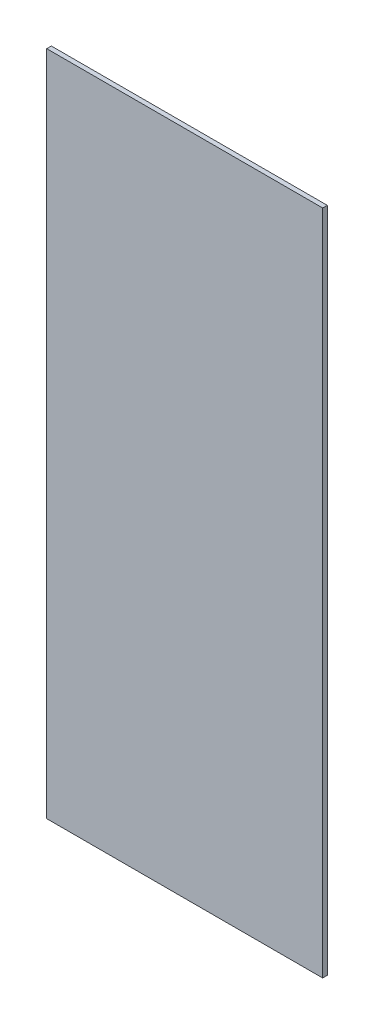
SolidWorks part; units mm, degrees
material "1060 Alloy"
ref_plane "Front Plane" through (0, 0, 0) normal (0, 0, 1) x (1, 0, 0)
ref_plane "Top Plane" through (0, 0, 0) normal (0, 1, 0) x (1, 0, 0)
ref_plane "Right Plane" through (0, 0, 0) normal (1, 0, 0) x (0, 0, -1)
sketch "Sketch1" plane through (0, 0, 0) normal (0, 0, 1) x (1, 0, 0)
  line L1 (-60, 145) -> (60, 145)
  line L2 (-60, 145) -> (-60, -145)
  line L3 (-60, -145) -> (60, -145)
  line L4 (60, 145) -> (60, -145)
  line L5 (-60, 145) -> (60, -145) construction
  line L6 (-60, -145) -> (60, 145) construction
  point P0 (0, 0)
  dimension "D1" = 120
  dimension "D2" = 290
extrude "Boss-Extrude1" add sketch "Sketch1" along normal blind 2
